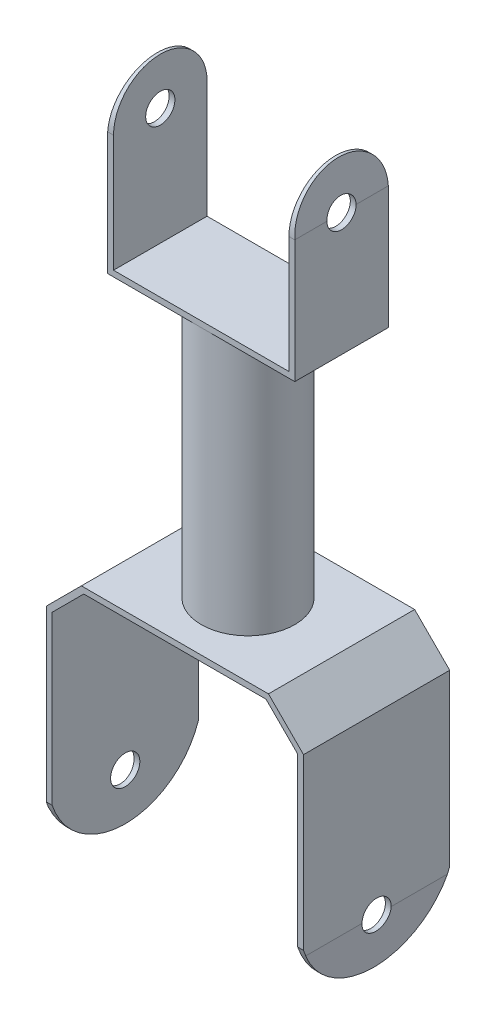
SolidWorks part; units mm, degrees
ref_plane "Front Plane" through (0, 0, 0) normal (0, 0, 1) x (1, 0, 0)
ref_plane "Top Plane" through (0, 0, 0) normal (0, 1, 0) x (1, 0, 0)
ref_plane "Right Plane" through (0, 0, 0) normal (1, 0, 0) x (0, 0, -1)
sketch "Sketch1" plane through (0, 0, 0) normal (0, 0, 1) x (1, 0, 0)
  line L0 (0, 0) -> (0, 101) construction
  line L1 (-22, 0) -> (22, 0) construction
  line L2 (-16, 101) -> (16, 101) construction
  line L3 (-16, 101) -> (-16, 80)
  line L5 (16, 80) -> (16, 101)
  line L6 (-16, 80) -> (16, 80)
  line L7 (-22, 0) -> (-22, 30)
  line L8 (-22, 30) -> (-16, 36)
  line L9 (-16, 36) -> (16, 36)
  line L10 (16, 36) -> (22, 30)
  line L11 (22, 30) -> (22, 0)
  line L12 (-15, 101) -> (-15, 81)
  line L13 (-15, 81) -> (15, 81)
  line L14 (15, 81) -> (15, 101)
  line L15 (-21, 0) -> (-21, 29.5858)
  line L16 (-21, 29.5858) -> (-15.5858, 35)
  line L17 (-15.5858, 35) -> (15.5858, 35)
  line L18 (15.5858, 35) -> (21, 29.5858)
  line L19 (21, 29.5858) -> (21, 0)
  line L22 (-15, 109) -> (-15, 101)
  line L23 (15, 101) -> (15, 109)
  line L24 (15, 109) -> (15.5, 109)
  line L27 (-21.5, -8) -> (-21, -8)
  line L28 (-21, -8) -> (-21, 0)
  line L29 (21, 0) -> (21, -8)
  line L30 (21, -8) -> (21.5, -8)
  line L32 (-15, 109) -> (-15.5, 109)
  line L33 (-15.5, 109) -> (-16, 101)
  line L34 (16, 101) -> (15.5, 109)
  line L35 (-22, 0) -> (-21.5, -8)
  line L36 (22, 0) -> (21.5, -8)
  point P6 (0, 0)
  point P9 (0, 101)
  dimension "D1" = 101
  dimension "D2" = 1
  dimension "D5" = 8
  dimension "D3" = 1
extrude "Boss-Extrude1" add sketch "Sketch1" along normal mid plane 25
sketch "Sketch3" plane through (22, 0, 0) normal (1, 0, 0) x (0, 0, -1)
  line L0 (0, 110) -> (0, 80) construction
  line L2 (-12.5, 80) -> (12.5, 80) construction
  line L5 (0, 110) -> (0, 102) construction
  line L6 (-8, 80) -> (-12.5, 80)
  line L7 (-12.5, 80) -> (-12.5, 110.5)
  line L8 (-12.5, 110.5) -> (12.5, 110.5)
  line L9 (12.5, 110.5) -> (12.5, 80)
  line L10 (12.5, 80) -> (8, 80)
  line L14 (-12.5, 101) -> (12.5, 101) construction
  line L18 (-12.5, 36) -> (-17.5, 36)
  line L19 (-17.5, 36) -> (-17.5, -14.4188)
  line L20 (-17.5, -14.4188) -> (17.5, -14.4188)
  line L21 (17.5, -14.4188) -> (17.5, 36)
  line L22 (17.5, 36) -> (12.5, 36)
  line L23 (-12.5, 36) -> (-12.5, 1)
  line L25 (12.5, 36) -> (12.5, 1)
  line L27 (-8, 80) -> (-8, 101)
  line L29 (8, 80) -> (8, 101)
  arc A5 (-12.5, 1) -> (12.5, 1) centre (0, 5.1692) ccw
  circle A6 centre (0, 0) radius 2.5
  circle A7 centre (0, 101) radius 2.5
  arc A8 (-8, 101) -> (8, 101) centre (0, 101) cw
  point P27 (0, 0)
  point P28 (0, 109)
  point P37 (0, 0)
  point P38 (0, 0)
  point P39 (0, 0)
  point P40 (0, 0)
  dimension "D1" = 101
  dimension "D2" = 8
extrude "Cut-Extrude1" cut sketch "Sketch3" against normal through all both and the other way through all
sketch "Sketch4" plane through (0, 36, 0) normal (0, 1, 0) x (1, 0, 0)
  circle A0 centre (0, 0) radius 8
  circle A1 centre (0, 0) radius 6.0004
extrude "Boss-Extrude2" add sketch "Sketch4" along normal blind 44
